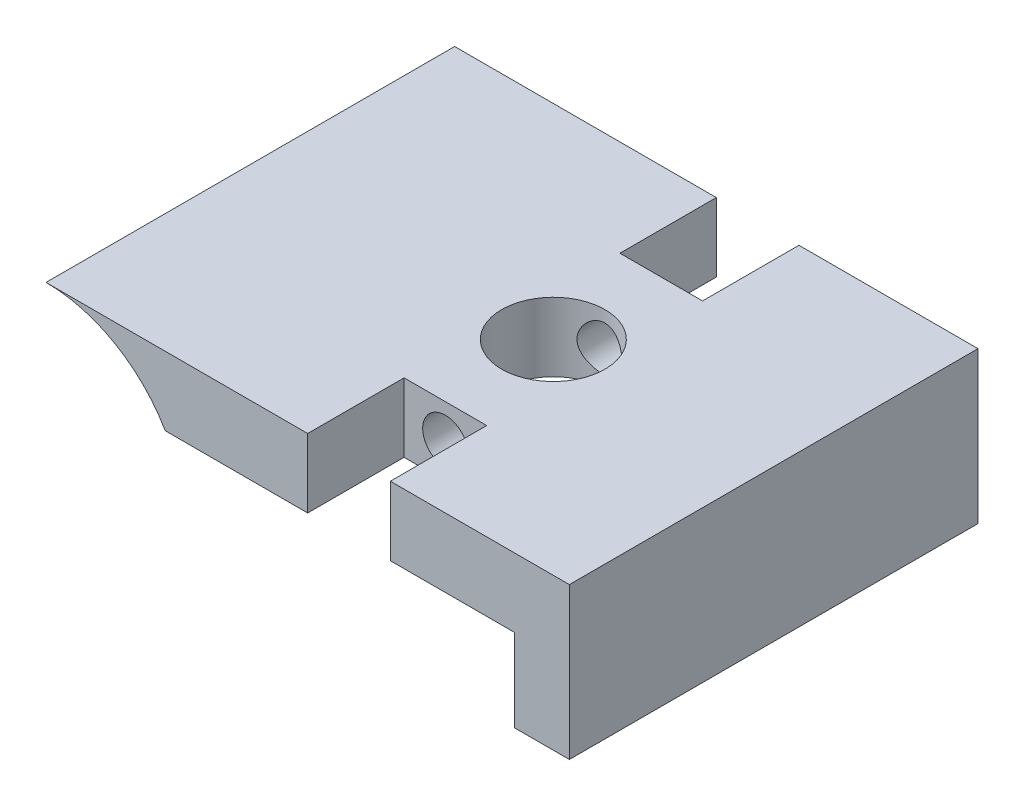
SolidWorks part; units mm, degrees
ref_plane "Front Plane" through (0, 0, 0) normal (0, 0, 1) x (1, 0, 0)
ref_plane "Top Plane" through (0, 0, 0) normal (0, 1, 0) x (1, 0, 0)
ref_plane "Right Plane" through (0, 0, 0) normal (1, 0, 0) x (0, 0, -1)
sketch "Sketch3" plane through (0, 0, 0) normal (0, 0, 1) x (1, 0, 0)
  line L0 (-19, 2.5) -> (-10.3397, -2.5) construction
  line L1 (-10.3397, -2.5) -> (19, -2.5)
  line L3 (-19, 2.5) -> (19, 2.5)
  line L4 (19, -2.5) -> (19, 2.5)
  line L5 (-11.9471, -1.572) -> (19, 2.5) construction
  line L6 (-19, 2.5) -> (19, -2.5) construction
  arc A0 (-19, 2.5) -> (-10.3397, -2.5) centre (-19, -7.5) cw
  point P0 (0, 0)
  point P6 (0, 2.5)
  dimension "D3" = 10
  dimension "D1" = 38
  dimension "D2" = 150
  dimension "D4" = 5
extrude "Boss-Extrude1" add sketch "Sketch3" along normal mid plane 29.67
sketch "Sketch4" plane through (0, 0, 14.835) normal (0, 0, 1) x (1, 0, 0)
  line L0 (19, -2.5) -> (19, 2.5) construction
  line L1 (19, 2.5) -> (-19, 2.5) construction
  line L2 (6, -2.5) -> (0, -2.5)
  line L3 (6, -2.5) -> (6, 2.5)
  line L4 (6, 2.5) -> (0, 2.5)
  line L5 (0, -2.5) -> (0, 2.5)
  line L6 (6, -2.5) -> (0, 2.5) construction
  line L7 (6, 2.5) -> (0, -2.5) construction
  circle A2 centre (3, 0) radius 1.65
  point P0 (19, 0)
  dimension "D1" = 3.3
  dimension "D5" = 16
extrude "Cut-Extrude1" cut sketch "Sketch4" against normal up to next contours A2 region at (3, 0, 14.835)
extrude "Cut-Extrude3" cut sketch "Sketch4<3>" against normal blind 7
sketch "Sketch4<3>" plane through (0, 0, 14.835) normal (0, 0, 1) x (1, 0, 0) same geometry as "Sketch4"
mirror "Mirror1" about plane through (0, 0, 0) normal (0, 0, 1) of "Cut-Extrude3"
sketch "Sketch5" plane through (0, 2.5, 0) normal (0, 1, 0) x (1, 0, 0)
  line L0 (19, -14.835) -> (19, 14.835) construction
  circle A0 centre (3, 0) radius 3.75
  point P7 (19, 0)
  dimension "D2" = 7.5
  dimension "D1" = 16
extrude "Cut-Extrude2" cut sketch "Sketch5" against normal up to next
sketch "Sketch6" plane through (0, 0, 14.835) normal (0, 0, 1) x (1, 0, 0)
  line L0 (19, -2.5) -> (19, -8.5)
  line L1 (19, -8.5) -> (15, -8.5)
  line L2 (15, -8.5) -> (15, -2.5)
  line L3 (6, -2.5) -> (19, -2.5) construction
  line L4 (15, -2.5) -> (19, -2.5)
  dimension "D1" = 6
  dimension "D2" = 4
extrude "Boss-Extrude2" add sketch "Sketch6" against normal up to surface (29.67 mm away) up to face at (12.5, 0, -14.835)
